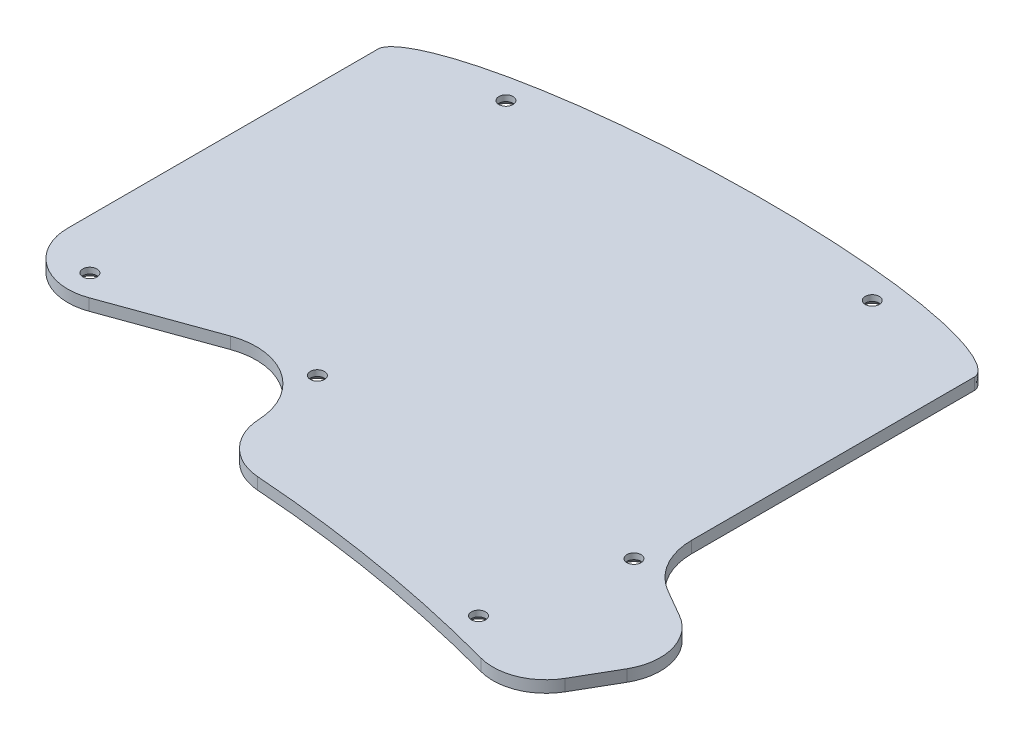
SolidWorks part; units mm, degrees
ref_plane "Front Plane" through (0, 0, 0) normal (0, 0, 1) x (1, 0, 0)
ref_plane "Top Plane" through (0, 0, 0) normal (0, 1, 0) x (1, 0, 0)
ref_plane "Right Plane" through (0, 0, 0) normal (1, 0, 0) x (0, 0, -1)
ref_plane "Plane1" through (0, -18, 0) normal (0, -1, 0) x (-1, 0, 0)
sketch "Sketch1" plane through (0, -18, 0) normal (0, -1, 0) x (-1, 0, 0)
  line L0 (3.5375, 46.5187) -> (2.5375, 46.5187) construction
  line L1 (2.5375, 46.5187) -> (2.5375, 21.3832) construction
  line L2 (-2.9636, 11.8563) -> (-7.606, 9.1767) construction
  line L3 (-10.9016, -3.1172) -> (-7.0614, -9.7705) construction
  line L4 (71.9636, 12.2185) -> (89.6698, 5.8152) construction
  line L5 (101.7306, 14.2787) -> (101.7306, 22.9312) construction
  line L6 (101.7306, 22.9312) -> (100.7306, 22.9312) construction
  line L7 (100.7306, 22.9312) -> (100.7306, 14.2787) construction
  line L8 (87.6444, 7.611) -> (72.3037, 13.1589) construction
  line L9 (-6.1953, -9.2706) -> (-10.0355, -2.6173) construction
  line L10 (-7.1061, 8.3106) -> (-2.4637, 10.9902) construction
  line L11 (3.5375, 21.3832) -> (3.5375, 46.5187) construction
  line L19 (2.5375, 69.5982) -> (2.5375, 59.5187) construction
  line L21 (2.5375, 59.5187) -> (3.5375, 59.5187) construction
  line L22 (3.5375, 59.5187) -> (3.5375, 69.5723) construction
  line L23 (100.7306, 67.1646) -> (100.7306, 43.9312) construction
  line L34 (100.7306, 43.9312) -> (101.7306, 43.9312) construction
  line L35 (101.7306, 43.9312) -> (101.7306, 67.1387) construction
  line L48 (3.5375, 46.5187) -> (2.5375, 46.5187)
  line L65 (2.5375, 46.5187) -> (2.5375, 21.3832)
  line L66 (-2.9636, 11.8563) -> (-7.606, 9.1767)
  line L67 (-10.9016, -3.1172) -> (-7.0614, -9.7705)
  line L74 (71.9636, 12.2185) -> (89.6698, 5.8152)
  line L75 (101.7306, 14.2787) -> (101.7306, 22.9312)
  line L76 (101.7306, 22.9312) -> (100.7306, 22.9312)
  line L77 (100.7306, 22.9312) -> (100.7306, 14.2787)
  line L78 (87.6444, 7.611) -> (72.3037, 13.1589)
  line L79 (-6.1953, -9.2706) -> (-10.0355, -2.6173)
  line L80 (-7.1061, 8.3106) -> (-2.4637, 10.9902)
  line L81 (3.5375, 21.3832) -> (3.5375, 46.5187)
  line L82 (2.5375, 69.5982) -> (2.5375, 59.5187)
  line L83 (2.5375, 59.5187) -> (3.5375, 59.5187)
  line L84 (3.5375, 59.5187) -> (3.5375, 69.5723)
  line L85 (100.7306, 67.1646) -> (100.7306, 43.9312)
  line L86 (100.7306, 43.9312) -> (101.7306, 43.9312)
  line L87 (101.7306, 43.9312) -> (101.7306, 67.1387)
  line L89 (2.5375, 59.5187) -> (3.5375, 59.5187)
  line L90 (2.5375, 59.5187) -> (2.5375, 46.5187)
  line L91 (2.5375, 46.5187) -> (3.5375, 46.5187)
  line L92 (3.5375, 59.5187) -> (3.5375, 46.5187)
  line L93 (100.7306, 43.9312) -> (101.7306, 43.9312)
  line L94 (100.7306, 43.9312) -> (100.7306, 22.9312)
  line L95 (100.7306, 22.9312) -> (101.7306, 22.9312)
  line L96 (101.7306, 43.9312) -> (101.7306, 22.9312)
  arc A0 (-2.9636, 11.8563) -> (2.5375, 21.3832) centre (-8.4625, 21.3832) ccw construction
  arc A1 (-7.606, 9.1767) -> (-10.9016, -3.1172) centre (-3.1069, 1.3819) ccw construction
  arc A2 (-7.0614, -9.7705) -> (3.0818, -13.9595) centre (0.7334, -5.2713) ccw construction
  arc A3 (48.8818, -6.2135) -> (3.0818, -13.9595) centre (66.0135, -246.7815) ccw construction
  arc A4 (48.8818, -6.2135) -> (57.2336, 2.3634) centre (48.2425, 2.7638) ccw construction
  arc A5 (71.9636, 12.2185) -> (57.2336, 2.3634) centre (68.2227, 1.8741) ccw construction
  arc A6 (89.6698, 5.8152) -> (101.7306, 14.2787) centre (92.7306, 14.2787) ccw construction
  arc A7 (99.5118, 10.0342) -> (100.7306, 14.2787) centre (92.7306, 14.2787) ccw construction
  arc A8 (96.3492, 10.47) -> (99.5118, 10.0342) centre (98.0284, 10.9627) ccw construction
  arc A9 (96.3492, 10.47) -> (89.9864, 9.3612) centre (93.2306, 9.5551) ccw construction
  arc A10 (87.6444, 7.611) -> (89.9864, 9.3612) centre (88.2395, 9.2567) ccw construction
  arc A11 (72.3037, 13.1589) -> (64.2101, 13.1834) centre (68.2227, 1.8741) ccw construction
  arc A12 (61.9119, 14.4747) -> (64.2101, 13.1834) centre (63.6249, 14.8326) ccw construction
  arc A13 (61.9119, 14.4747) -> (57.3666, 10.86) centre (58.7306, 13.8099) ccw construction
  arc A21 (58.1073, 8.3301) -> (57.3666, 10.86) centre (56.6322, 9.2716) ccw construction
  arc A22 (58.1073, 8.3301) -> (56.2346, 2.4079) centre (68.2227, 1.8741) ccw construction
  arc A23 (48.8107, -5.216) -> (56.2346, 2.4079) centre (48.2425, 2.7638) ccw construction
  arc A24 (48.8107, -5.216) -> (14.89, -10.0618) centre (66.0135, -246.7815) ccw construction
  arc A25 (12.7765, -8.2075) -> (14.89, -10.0618) centre (14.5206, -8.3513) ccw construction
  arc A26 (12.7765, -8.2075) -> (6.7611, -9.6299) centre (9.5375, -7.9406) ccw construction
  arc A27 (5.7019, -12.2344) -> (6.7611, -9.6299) centre (5.2661, -10.5396) ccw construction
  arc A42 (5.7019, -12.2344) -> (2.8209, -12.9942) centre (66.0135, -246.7815) ccw construction
  arc A43 (-6.1953, -9.2706) -> (2.8209, -12.9942) centre (0.7334, -5.2713) ccw construction
  arc A73 (-7.1061, 8.3106) -> (-10.0355, -2.6173) centre (-3.1069, 1.3819) ccw construction
  arc A74 (-2.4637, 10.9902) -> (-0.5914, 12.3252) centre (-8.4625, 21.3832) ccw construction
  arc A75 (2.0198, 11.964) -> (-0.5914, 12.3252) centre (0.5564, 11.0043) ccw construction
  arc A76 (2.0198, 11.964) -> (4.928, 16.9907) centre (4.7375, 13.7463) ccw construction
  arc A77 (3.3133, 19.0744) -> (4.928, 16.9907) centre (5.0306, 18.7377) ccw construction
  arc A88 (3.3133, 19.0744) -> (3.5375, 21.3832) centre (-8.4625, 21.3832) ccw construction
  arc A90 (19.327, 72.6447) -> (17.2987, 74.6407) centre (17.5982, 72.9165) ccw construction
  arc A91 (19.327, 72.6447) -> (25.5115, 73.4505) centre (22.5375, 72.1398) ccw construction
  arc A92 (26.9481, 75.8985) -> (25.5115, 73.4505) centre (27.1128, 74.1563) ccw construction
  arc A93 (80.3395, 71.9158) -> (79.0483, 74.4448) centre (78.7827, 72.7151) ccw construction
  arc A94 (80.3395, 71.9158) -> (86.4665, 70.7342) centre (83.2306, 70.4313) ccw construction
  arc A95 (88.6201, 72.5983) -> (86.4665, 70.7342) centre (88.2088, 70.8973) ccw construction
  arc A96 (-2.9636, 11.8563) -> (2.5375, 21.3832) centre (-8.4625, 21.3832) ccw
  arc A97 (-7.606, 9.1767) -> (-10.9016, -3.1172) centre (-3.1069, 1.3819) ccw
  arc A98 (-7.0614, -9.7705) -> (3.0818, -13.9595) centre (0.7334, -5.2713) ccw
  arc A99 (48.8818, -6.2135) -> (3.0818, -13.9595) centre (66.0135, -246.7815) ccw
  arc A100 (48.8818, -6.2135) -> (57.2336, 2.3634) centre (48.2425, 2.7638) ccw
  arc A101 (71.9636, 12.2185) -> (57.2336, 2.3634) centre (68.2227, 1.8741) ccw
  arc A102 (89.6698, 5.8152) -> (101.7306, 14.2787) centre (92.7306, 14.2787) ccw
  arc A103 (99.5118, 10.0342) -> (100.7306, 14.2787) centre (92.7306, 14.2787) ccw
  arc A104 (96.3492, 10.47) -> (99.5118, 10.0342) centre (98.0284, 10.9627) ccw
  arc A105 (96.3492, 10.47) -> (89.9864, 9.3612) centre (93.2306, 9.5551) ccw
  arc A106 (87.6444, 7.611) -> (89.9864, 9.3612) centre (88.2395, 9.2567) ccw
  arc A107 (72.3037, 13.1589) -> (64.2101, 13.1834) centre (68.2227, 1.8741) ccw
  arc A108 (61.9119, 14.4747) -> (64.2101, 13.1834) centre (63.6249, 14.8326) ccw
  arc A109 (61.9119, 14.4747) -> (57.3666, 10.86) centre (58.7306, 13.8099) ccw
  arc A110 (58.1073, 8.3301) -> (57.3666, 10.86) centre (56.6322, 9.2716) ccw
  arc A111 (58.1073, 8.3301) -> (56.2346, 2.4079) centre (68.2227, 1.8741) ccw
  arc A112 (48.8107, -5.216) -> (56.2346, 2.4079) centre (48.2425, 2.7638) ccw
  arc A113 (48.8107, -5.216) -> (14.89, -10.0618) centre (66.0135, -246.7815) ccw
  arc A114 (12.7765, -8.2075) -> (14.89, -10.0618) centre (14.5206, -8.3513) ccw
  arc A115 (12.7765, -8.2075) -> (6.7611, -9.6299) centre (9.5375, -7.9406) ccw
  arc A116 (5.7019, -12.2344) -> (6.7611, -9.6299) centre (5.2661, -10.5396) ccw
  arc A117 (5.7019, -12.2344) -> (2.8209, -12.9942) centre (66.0135, -246.7815) ccw
  arc A118 (-6.1953, -9.2706) -> (2.8209, -12.9942) centre (0.7334, -5.2713) ccw
  arc A119 (-7.1061, 8.3106) -> (-10.0355, -2.6173) centre (-3.1069, 1.3819) ccw
  arc A120 (-2.4637, 10.9902) -> (-0.5914, 12.3252) centre (-8.4625, 21.3832) ccw
  arc A121 (2.0198, 11.964) -> (-0.5914, 12.3252) centre (0.5564, 11.0043) ccw
  arc A122 (2.0198, 11.964) -> (4.928, 16.9907) centre (4.7375, 13.7463) ccw
  arc A123 (3.3133, 19.0744) -> (4.928, 16.9907) centre (5.0306, 18.7377) ccw
  arc A124 (3.3133, 19.0744) -> (3.5375, 21.3832) centre (-8.4625, 21.3832) ccw
  arc A125 (19.327, 72.6447) -> (17.2987, 74.6407) centre (17.5982, 72.9165) ccw
  arc A126 (19.327, 72.6447) -> (25.5115, 73.4505) centre (22.5375, 72.1398) ccw
  arc A127 (26.9481, 75.8985) -> (25.5115, 73.4505) centre (27.1128, 74.1563) ccw
  arc A128 (80.3395, 71.9158) -> (79.0483, 74.4448) centre (78.7827, 72.7151) ccw
  arc A129 (80.3395, 71.9158) -> (86.4665, 70.7342) centre (83.2306, 70.4313) ccw
  arc A130 (88.6201, 72.5983) -> (86.4665, 70.7342) centre (88.2088, 70.8973) ccw
  spline S0 degree 3 poles (3899.3998, -822.1903) (5.5841, 61.1512) (2.5122, 67.3283) (3.582, 69.6988) (3.5979, 69.7282) (3.6492, 69.814) (3.6882, 69.8682) (3.8132, 70.0256) (3.9052, 70.1212) (4.1943, 70.393) (4.4056, 70.5549) (5.0614, 71.0066) (5.5225, 71.259) (6.4661, 71.7207) (6.9495, 71.9279) (7.931, 72.3125) (8.4288, 72.4893) (9.926, 72.9834) (10.934, 73.2666) (12.9619, 73.7775) (13.982, 74.0045) (125.5269, 96.5124) (285.8926, -113.8109) (-486.7922, 4030.3663) knots -0.073548 -0.073548 -0.073548 -0.073548 0.000977 0.000977 0.001953 0.001953 0.003906 0.003906 0.007812 0.007812 0.015625 0.015625 0.03125 0.03125 0.046875 0.046875 0.0625 0.0625 0.09375 0.09375 0.125 0.125 3.496518 3.496518 3.496518 3.496518 only from (3.5375, 69.5723) to (17.2987, 74.6407) construction
  spline S1 degree 3 poles (-477.1083, -3877.3486) (-250.6602, -122.6192) (-109.5374, 63.4053) (31.5962, 76.3247) (35.7511, 76.55) (44.0555, 76.778) (52.3546, 76.7795) (60.6437, 76.3692) (68.9275, 75.7323) (73.0667, 75.3025) (204.4615, 56.7015) (338.8353, -112.6201) (-1939.6539, -3355.4068) knots -3.867215 -3.867215 -3.867215 -3.867215 0.25 0.25 0.375 0.375 0.5 0.625 0.625 0.75 0.75 4.596546 4.596546 4.596546 4.596546 only from (26.9481, 75.8985) to (79.0483, 74.4448) construction
  spline S2 degree 3 poles (1249.0887, 3890.4335) (-183.7081, -100.6963) (-18.8477, 99.9123) (90.5626, 72.1105) (91.5733, 71.8321) (93.5794, 71.2182) (94.5733, 70.8839) (96.0407, 70.3155) (96.5252, 70.115) (97.4808, 69.6829) (97.9521, 69.4516) (98.869, 68.9422) (99.3167, 68.665) (99.9393, 68.1841) (100.1392, 68.0129) (100.41, 67.7271) (100.4955, 67.6271) (100.6082, 67.4654) (100.6431, 67.4097) (100.6877, 67.3218) (100.7012, 67.2919) (101.4302, 65.2399) (101.7532, 57.7763) (-3890.1992, 195.7579) knots -2.45843 -2.45843 -2.45843 -2.45843 0.875 0.875 0.90625 0.90625 0.9375 0.9375 0.953125 0.953125 0.96875 0.96875 0.984375 0.984375 0.992188 0.992188 0.996094 0.996094 0.998047 0.998047 0.999023 0.999023 1.062703 1.062703 1.062703 1.062703 only from (88.6201, 72.5983) to (100.7306, 67.1646) construction
  spline S3 degree 3 poles (-3249.4703, 2247.9507) (12.2588, 13.1567) (104.5699, 58.2459) (101.6331, 67.6686) (101.5759, 67.7904) (101.3723, 68.1426) (101.1991, 68.3521) (100.8236, 68.7399) (100.6216, 68.9164) (100.2008, 69.2489) (99.9816, 69.4045) (99.306, 69.8491) (98.8369, 70.1129) (97.8772, 70.6032) (97.3882, 70.8281) (95.903, 71.4617) (94.8899, 71.8297) (92.8442, 72.5008) (91.8102, 72.8032) (88.692, 73.6407) (86.5884, 74.1082) (82.3631, 74.9308) (80.2384, 75.285) (73.8497, 76.2205) (69.5658, 76.6778) (60.9853, 77.3535) (56.684, 77.57) (48.0793, 77.7822) (43.7782, 77.778) (37.3289, 77.5895) (35.1795, 77.496) (30.8816, 77.2388) (28.7355, 77.0753) (24.4582, 76.6638) (22.3259, 76.4161) (18.0784, 75.8065) (15.963, 75.4464) (12.8106, 74.7679) (11.7634, 74.5184) (9.6792, 73.9504) (8.6409, 73.6322) (7.1217, 73.0749) (6.621, 72.8755) (5.6365, 72.4364) (5.1523, 72.1974) (4.4477, 71.7872) (4.2157, 71.6411) (3.7704, 71.3281) (3.5564, 71.1612) (3.2566, 70.8856) (3.1602, 70.7894) (2.9775, 70.585) (2.8913, 70.4766) (-2.8823, 61.8111) (40.625, 9.4767) (3976.1662, 517.5782) knots -0.277833 -0.277833 -0.277833 -0.277833 0.003906 0.003906 0.007812 0.007812 0.015625 0.015625 0.023437 0.023437 0.03125 0.03125 0.046875 0.046875 0.0625 0.0625 0.09375 0.09375 0.125 0.125 0.1875 0.1875 0.25 0.25 0.375 0.375 0.5 0.5 0.625 0.625 0.6875 0.6875 0.75 0.75 0.8125 0.8125 0.875 0.875 0.90625 0.90625 0.9375 0.9375 0.953125 0.953125 0.96875 0.96875 0.976562 0.976562 0.984375 0.984375 0.988281 0.988281 0.992187 0.992187 1.285678 1.285678 1.285678 1.285678 only from (101.7306, 67.1387) to (2.5375, 69.5982) construction
  spline S4 degree 3 poles (3.5375, 69.5723) (3.5412, 69.6062) (3.5543, 69.6375) (3.582, 69.6988) (3.5979, 69.7282) (3.6492, 69.814) (3.6882, 69.8682) (3.8132, 70.0256) (3.9052, 70.1212) (4.1943, 70.393) (4.4056, 70.5549) (5.0614, 71.0066) (5.5225, 71.259) (6.4661, 71.7207) (6.9495, 71.9279) (7.931, 72.3125) (8.4288, 72.4893) (9.926, 72.9834) (10.934, 73.2666) (12.9619, 73.7775) (13.982, 74.0045) (15.7682, 74.3649) (16.5324, 74.5076) (17.2987, 74.6407) knots 0 0 0 0 0.000977 0.000977 0.001953 0.001953 0.003906 0.003906 0.007812 0.007812 0.015625 0.015625 0.03125 0.03125 0.046875 0.046875 0.0625 0.0625 0.09375 0.09375 0.125 0.125 0.14824 0.14824 0.14824 0.14824
  spline S5 degree 3 poles (26.9481, 75.8985) (27.1112, 75.9139) (27.2744, 75.9291) (31.5962, 76.3247) (35.7511, 76.55) (44.0555, 76.778) (52.3546, 76.7795) (60.6437, 76.3692) (68.9275, 75.7323) (73.0667, 75.3025) (77.8175, 74.63) (78.433, 74.5393) (79.0483, 74.4448) knots 0.245096 0.245096 0.245096 0.245096 0.25 0.25 0.375 0.375 0.5 0.625 0.625 0.75 0.75 0.768598 0.768598 0.768598 0.768598
  spline S6 degree 3 poles (88.6201, 72.5983) (88.9293, 72.5236) (89.2381, 72.4471) (90.5626, 72.1105) (91.5733, 71.8321) (93.5794, 71.2182) (94.5733, 70.8839) (96.0407, 70.3155) (96.5252, 70.115) (97.4808, 69.6829) (97.9521, 69.4516) (98.869, 68.9422) (99.3167, 68.665) (99.9393, 68.1841) (100.1392, 68.0129) (100.41, 67.7271) (100.4955, 67.6271) (100.6082, 67.4654) (100.6431, 67.4097) (100.6877, 67.3218) (100.7012, 67.2919) (100.7233, 67.2299) (100.7342, 67.1976) (100.7306, 67.1646) knots 0.865518 0.865518 0.865518 0.865518 0.875 0.875 0.90625 0.90625 0.9375 0.9375 0.953125 0.953125 0.96875 0.96875 0.984375 0.984375 0.992188 0.992188 0.996094 0.996094 0.998047 0.998047 0.999023 0.999023 1 1 1 1
  spline S7 degree 3 poles (101.7306, 67.1387) (101.7353, 67.2751) (101.7134, 67.4109) (101.6331, 67.6686) (101.5759, 67.7904) (101.3723, 68.1426) (101.1991, 68.3521) (100.8236, 68.7399) (100.6216, 68.9164) (100.2008, 69.2489) (99.9816, 69.4045) (99.306, 69.8491) (98.8369, 70.1129) (97.8772, 70.6032) (97.3882, 70.8281) (95.903, 71.4617) (94.8899, 71.8297) (92.8442, 72.5008) (91.8102, 72.8032) (88.692, 73.6407) (86.5884, 74.1082) (82.3631, 74.9308) (80.2384, 75.285) (73.8497, 76.2205) (69.5658, 76.6778) (60.9853, 77.3535) (56.684, 77.57) (48.0793, 77.7822) (43.7782, 77.778) (37.3289, 77.5895) (35.1795, 77.496) (30.8816, 77.2388) (28.7355, 77.0753) (24.4582, 76.6638) (22.3259, 76.4161) (18.0784, 75.8065) (15.963, 75.4464) (12.8106, 74.7679) (11.7634, 74.5184) (9.6792, 73.9504) (8.6409, 73.6322) (7.1217, 73.0749) (6.621, 72.8755) (5.6365, 72.4364) (5.1523, 72.1974) (4.4477, 71.7872) (4.2157, 71.6411) (3.7704, 71.3281) (3.5564, 71.1612) (3.2566, 70.8856) (3.1602, 70.7894) (2.9775, 70.585) (2.8913, 70.4766) (2.6638, 70.1352) (2.547, 69.8765) (2.5375, 69.5982) knots 0 0 0 0 0.003906 0.003906 0.007812 0.007812 0.015625 0.015625 0.023437 0.023437 0.03125 0.03125 0.046875 0.046875 0.0625 0.0625 0.09375 0.09375 0.125 0.125 0.1875 0.1875 0.25 0.25 0.375 0.375 0.5 0.5 0.625 0.625 0.6875 0.6875 0.75 0.75 0.8125 0.8125 0.875 0.875 0.90625 0.90625 0.9375 0.9375 0.953125 0.953125 0.96875 0.96875 0.976562 0.976562 0.984375 0.984375 0.988281 0.988281 0.992187 0.992187 1 1 1 1
extrude "Boss-Extrude1" add sketch "Sketch1" along normal blind 2 contours S6 A130 A129 A128 S5 A127 A126 A125 S4 L84 L92 L81 A124 A123 A122 A121 A120 L80 A119 L79 A118 A117 A116 A115 A114 A113 A112 A111 A110 A109 A108 A107 L78 A106 A105 A104 A103 L77 L94 L85 | A123 A124 L81 L48 L65 A96 L66 A97 L67 A98 A99 A100 A101 L74 A102 L75 L76 L77 A103 A104 A105 A106 L78 A107 A108 A109 A110 A111 A112 A113 A114 A115 A116 A117 A118 L79 A119 L80 A120 A121 A122 | L87 S7 L82 L83 L84 S4 A125 A126 A127 S5 A128 A129 A130 S6 L85 L86 | L92 L83 L90 L48 | L96 L86 L94 L76 region at (-3.4084, -18, -33.951) region at (-46.8071, -18, -35.8063) region at (-3.0375, -18, -53.0187) region at (-3.0375, -18, -60.5668) region at (-101.2306, -18, -33.4312)
hole_wizard "CSK for M2 Flat Head Machine Screw2" positions "3DSketch8" profile "Sketch7" countersink size "M2" standard "ANSI Metric" end condition through all
sketch3d "3DSketch8"
  circle A0 centre (-22.5375, -18, -72.1398) radius 1.75 construction
  circle A1 centre (-83.2306, -18, -70.4313) radius 1.75 construction
  circle A2 centre (-93.2306, -18, -9.5551) radius 1.75 construction
  circle A3 centre (-58.7306, -18, -13.8099) radius 1.75 construction
  circle A4 centre (-9.5375, -18, 7.9406) radius 1.75 construction
  circle A5 centre (-4.7375, -18, -13.7463) radius 1.75 construction
  point P37 (-22.5375, -20, -72.1398)
  point P39 (-83.2306, -20, -70.4313)
  point P41 (-93.2306, -20, -9.5551)
  point P43 (-58.7306, -20, -13.8099)
  point P45 (-9.5375, -20, 7.9406)
  point P47 (-4.7375, -20, -13.7463)
  point P57 (-22.5375, -19.75, -72.1398)
  point P61 (-83.2306, -19.75, -70.4313)
  point P65 (-93.2306, -19.75, -9.5551)
  point P69 (-58.7306, -19.75, -13.8099)
  point P73 (-9.5375, -19.75, 7.9406)
  point P76 (-4.7375, -19.75, -13.7463)
sketch "Sketch7" plane through (-22.5375, -20, -72.1398) normal (1, 0, 0) x (0, 0, -1)
  line L0 (0, 0) -> (0, 2)
  line L1 (0, 2) -> (1.2, 2)
  line L2 (1.2, 2) -> (1.2, 1)
  line L3 (1.2, 1) -> (2.2, 0)
  line L5 (2.2, 0) -> (0, 0)
  line L6 (-1.2, 1) -> (-2.2, 0) construction
  line L11 (0, -6.35) -> (0, 107.95) construction
  dimension "Thru Hole Dia." = 2.4
  dimension "Thru Hole Depth" = 2
  dimension "Near C'Sink Dia." = 4.4
  dimension "Near C'Sink Angle" = 90
move or copy body "Body-Move/Copy2" [suppressed] bodies to move or copy 110
move or copy body "Body-Move/Copy1" [suppressed] bodies to move or copy 110
